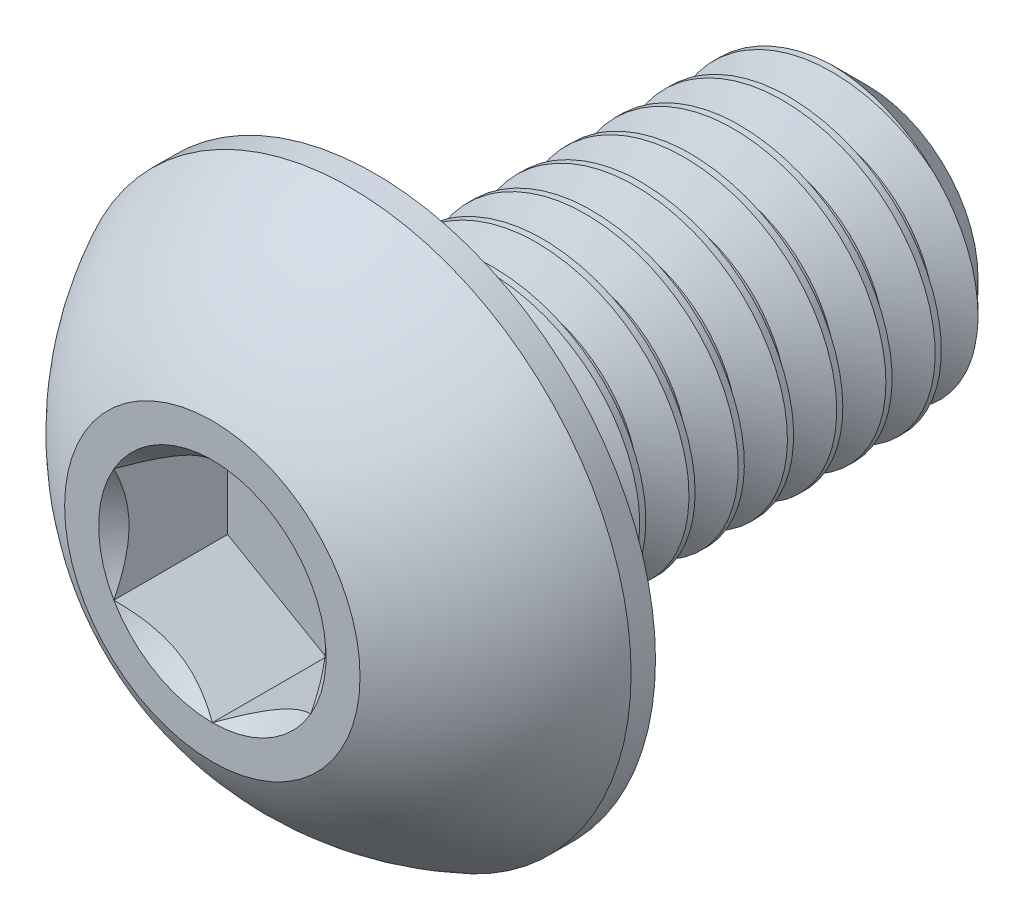
SolidWorks part; units mm, degrees
note: '?' marks a value the reader was unsure of.
ref_plane "Front" through (0, 0, 0) normal (0, 0, 1) x (1, 0, 0)
ref_plane "Top" through (0, 0, 0) normal (0, 1, 0) x (1, 0, 0)
ref_plane "Right" through (0, 0, 0) normal (1, 0, 0) x (0, 0, -1)
sketch "Profile Sketch" plane through (0, 0, 0) normal (1, 0, 0) x (0, 0, -1)
  line L2 (1.65, 1.5) -> (6.65, 1.5)
  line L3 (6.65, 1.5) -> (6.65, 0)
  line L4 (6.65, 0) -> (1.65, 0)
  line L6 (1.4025, 2.85) -> (1.65, 2.85) construction
  line L7 (6.65, 1.5) -> (6.65, -1.5) construction
  line L8 (0, 0) -> (1.65, 0) construction
  line L9 (1.65, 2.85) -> (1.65, -2.85) construction
  line L11 (1.65, 1.5) -> (1.65, 0)
  line L13 (0, 1) -> (0, -1) construction
  line L14 (0, 1) -> (0, 1.5) construction
  arc A3 (0, 1.5) -> (1.4025, 2.85) centre (2.7948, 0) cw construction
  dimension "D1" = 0.2475
revolve "Revolve1" add sketch "Profile Sketch" angle 360 mid plane about L4
sketch "Spirral Sketch" plane through (0, 0, -6.65) normal (0, 0, -1) x (-1, 0, 0)
  circle A0 centre (0, 0) radius 1.5
curve "Helix/Spiral1" pitch 0.5 height 5.5 turns 11
chamfer "Chamfer1" distance 0.375 angle 45 1 edges at (0, 1.5, -6.65)
sketch "Sketch7" plane through (0, 0, 0) normal (1, 0, 0) x (0, 0, -1)
  line L6 (1.4025, 2.85) -> (1.65, 2.85) construction
  line L8 (0, 0) -> (1.65, 0) construction
  line L11 (1.65, 2.85) -> (1.65, -2.85) construction
  line L12 (1.4025, 2.85) -> (1.65, 2.85)
  line L13 (0, 0) -> (1.65, 0)
  line L14 (0, 1) -> (0, -1) construction
  line L15 (1.65, 2.85) -> (1.65, 0)
  line L16 (0, 1.5) -> (0, 0)
  arc A2 (1.4025, 2.85) -> (0, 1.5) centre (2.7948, 0) ccw construction
  arc A3 (1.4025, 2.85) -> (0, 1.5) centre (2.7948, 0) ccw
revolve "Revolve2" add sketch "Sketch7" angle 360 mid plane about L13
sketch "Sketch5" plane through (0, 0, 0) normal (0, 0, 1) x (1, 0, 0)
  line L1 (1, -0.5774) -> (1, 0.5774)
  line L2 (1, 0.5774) -> (0, 1.1547)
  line L3 (0, 1.1547) -> (-1, 0.5774)
  line L4 (-1, 0.5774) -> (-1, -0.5774)
  line L5 (-1, -0.5774) -> (0, -1.1547)
  line L6 (0, -1.1547) -> (1, -0.5774)
  circle A0 centre (0, 0) radius 1 construction
extrude "Cut-Extrude2" cut sketch "Sketch5" against normal blind 1.155
sketch "Sketch6" plane through (0, 0, 0) normal (0, 0, 1) x (1, 0, 0)
  circle A0 centre (0, 0) radius 1.1547
extrude "Cut-Extrude3" cut sketch "Sketch6" against normal blind 1.155 draft 45
sketch "Sketch2" plane through (0, 0, 0) normal (1, 0, 0) x (0, 0, -1)
  line L0 (6.275, 1.5) -> (6.7125, 1.5)
  line L1 (6.7125, 1.5) -> (6.525, 1.1752)
  line L2 (6.525, 1.1752) -> (6.4625, 1.1752)
  line L3 (6.4625, 1.1752) -> (6.275, 1.5)
  line L4 (6.3688, 1.3376) -> (6.6188, 1.3376) construction
  dimension "D1" = 60
  dimension "D2" = 0.0625
  dimension "D3" = 0.25
sweep "Cut-Sweep1" cut profiles "Sketch2" path "Helix/Spiral1"
sketch "Sketch10" plane through (0, 0, 0) normal (1, 0, 0) x (0, 0, -1)
  line L0 (6.65, 1.5) -> (6.65, -1.5) construction
  point P0 (5.9, -1.5)
  dimension "D1" = 0.75
ref_axis "Center Axis 1" through (0, 0, -8.1113) along (0, 0, 1)?
ref_plane "Contact Plane 1" through (0, 0, -1.65) normal (0, 0, -1) x (-1, 0, 0)
ref_plane "Contact Plane 2" through (0, 0, 0) normal (0, 0, 1) x (1, 0, 0)
equation "\"D3@Helix/Spiral1\" = \"Length@Profile Sketch\" + \"D4@Helix/Spiral1\""
equation "\"D2@Sketch2\" = \"D4@Helix/Spiral1\" * .125"
equation "\"D3@Sketch2\" = \"D4@Helix/Spiral1\" * .5"
equation "\"D1@Chamfer1\" = \"D4@Helix/Spiral1\" * .75"
equation "\"D1@Cut-Extrude2\" = \"Head Ht@Profile Sketch\" * .7"
equation "\"D1@Profile Sketch\" = \"Head Ht@Profile Sketch\" * .15"
equation "\"D1@Sketch10\" = \"D4@Helix/Spiral1\" * 1.5"
equation "\"D1@Cut-Extrude3\" = \"D1@Cut-Extrude2\""
